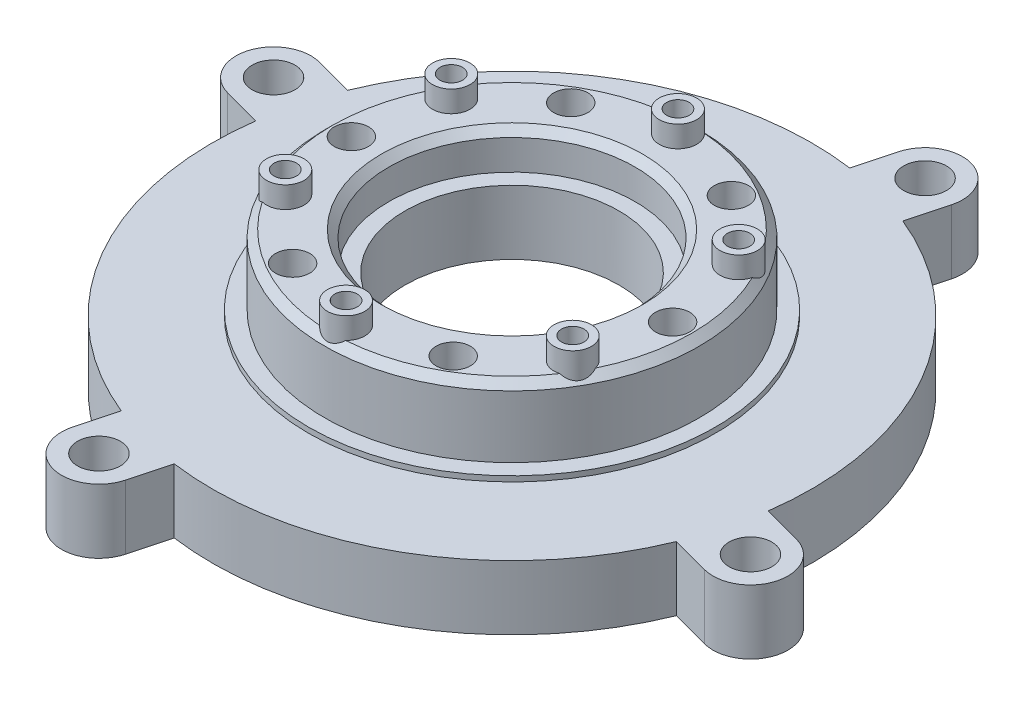
SolidWorks part; units mm, degrees
material "Like ABS"
ref_plane "Front Plane" through (0, 0, 0) normal (0, 0, 1) x (1, 0, 0)
ref_plane "Top Plane" through (0, 0, 0) normal (0, 1, 0) x (1, 0, 0)
ref_plane "Right Plane" through (0, 0, 0) normal (1, 0, 0) x (0, 0, -1)
sketch "Sketch1" plane through (0, 0, 0) normal (0, 1, 0) x (1, 0, 0)
  circle A0 centre (0, 0) radius 28
  dimension "D1" = 56
extrude "Boss-Extrude1" add sketch "Sketch1" along normal blind 6
sketch "Sketch2" plane through (0, 6, 0) normal (0, 1, 0) x (1, 0, 0)
  circle A0 centre (0, 0) radius 19
  dimension "D1" = 38
extrude "Boss-Extrude2" add sketch "Sketch2" along normal blind 0.5
sketch "Sketch3" plane through (0, 6.5, 0) normal (0, 1, 0) x (1, 0, 0)
  circle A0 centre (0, 0) radius 17.5
  dimension "D1" = 35
extrude "Boss-Extrude3" add sketch "Sketch3" along normal blind 6.5
sketch "Sketch4" plane through (0, 13, 0) normal (0, 1, 0) x (1, 0, 0)
  line L0 (0, 15.5) -> (0, 0) construction
  line L1 (0, 0) -> (7.75, 13.4234) construction
  circle A0 centre (0, 15.5) radius 1.05
  dimension "D3" = 2.1
  dimension "D1" = 30
  dimension "D2" = 15.5
extrude "Cut-Extrude1" cut sketch "Sketch4" against normal blind 3
pattern_circular "CirPattern1" count 6 over 360 about axis through (0, 13, 0) along (0, -1, 0) of "Cut-Extrude1"
sketch "Sketch5" plane through (0, 13, 0) normal (0, 1, 0) x (1, 0, 0)
  circle A0 centre (0, 0) radius 11.5
  dimension "D1" = 23
extrude "Cut-Extrude2" cut sketch "Sketch5" against normal blind 3.5
sketch "Sketch6" plane through (0, 9.5, 0) normal (0, 1, 0) x (1, 0, 0)
  circle A0 centre (0, 0) radius 10
  dimension "D1" = 20
extrude "Cut-Extrude3" cut sketch "Sketch6" against normal up to surface (9.5 mm away) up to face at (0, 0, 28)
sketch "Sketch7" plane through (0, 13, 0) normal (0, 1, 0) x (1, 0, 0)
  line L0 (0, 15.5) -> (0, 0) construction
  line L1 (0, 0) -> (7.5, 12.9904) construction
  circle A0 centre (7.5, 12.9904) radius 1.6
  dimension "D2" = 3.2
  dimension "D1" = 30
  dimension "D3" = 15
extrude "Cut-Extrude4" cut sketch "Sketch7" against normal up to surface (13 mm away) up to face at (0, 0, 10)
sketch "Sketch9" plane through (0, 0, 0) normal (0, -1, 0) x (1, 0, 0)
  line L1 (7.5, -9.6417) -> (4.6, -11.3161)
  line L2 (4.6, -11.3161) -> (4.6, -14.6647)
  line L3 (4.6, -14.6647) -> (7.5, -16.339)
  line L4 (7.5, -16.339) -> (10.4, -14.6647)
  line L5 (10.4, -14.6647) -> (10.4, -11.3161)
  line L6 (10.4, -11.3161) -> (7.5, -9.6417)
  circle A1 centre (7.5, -12.9904) radius 2.9 construction
  dimension "D1" = 5.8
extrude "Cut-Extrude10" cut sketch "Sketch9" against normal blind 5
chamfer "Chamfer1" distance 1 angle 45 1 edges at (0, 0, 10)
sketch "Sketch13" plane through (0, 6, 0) normal (0, 1, 0) x (1, 0, 0)
  line L0 (0, 25) -> (0, 0) construction
  line L1 (0, 0) -> (7.2469, 27.0459) construction
  line L2 (7.2469, 27.0459) -> (9.0587, 33.8074) construction
  line L6 (0, 0) -> (-27.0459, 7.2469) construction
  line L7 (-27.0459, 7.2469) -> (-33.8074, 9.0587) construction
  line L8 (0, 0) -> (-26.3114, 9.5766) construction
  line L9 (3.0505, 34.8668) -> (2.4404, 27.8935) construction
  line L10 (2.4404, 27.8935) -> (0, 0) construction
  line L11 (0, 0) -> (4.8621, 27.5746) construction
  line L12 (4.8621, 27.5746) -> (6.0777, 34.4683) construction
  line L19 (-26.3114, 9.5766) -> (-32.8892, 11.9707) construction
  line L20 (0, 0) -> (-25.3766, 11.8333) construction
  line L21 (-25.3766, 11.8333) -> (-31.7208, 14.7916) construction
  line L27 (4.7721, 31.3325) -> (3.0277, 24.8224)
  line L28 (3.0277, 24.8224) -> (9.7891, 23.0106)
  line L29 (9.7891, 23.0106) -> (11.5335, 29.5208)
  circle A0 centre (8.1528, 30.4267) radius 1.6
  circle A4 centre (0, 0) radius 28 construction
  arc A7 (11.5335, 29.5208) -> (4.7721, 31.3325) centre (8.1528, 30.4267) ccw
  dimension "D4" = 3.2
  dimension "D5" = 90
  dimension "D6" = 10
  dimension "D1" = 15
  dimension "D2" = 28
  dimension "D3" = 7
  dimension "D7" = 5
  dimension "D10" = 5
  dimension "D11" = 5
extrude "Boss-Extrude4" add sketch "Sketch13" against normal up to surface (6 mm away) up to face at (0, 0, 11)
sketch "Sketch14" plane through (0, 6, 0) normal (0, 1, 0) x (1, 0, 0)
  circle A0 centre (8.1528, 30.4267) radius 2
  dimension "D1" = 4
extrude "Cut-Extrude12" cut sketch "Sketch14" against normal blind 4
pattern_circular "CirPattern3" count 4 over 360 about axis through (0, 6, 0) along (0, -1, 0) of "Cut-Extrude12", "Boss-Extrude4"
sketch "Sketch15" plane through (0, 0, 0) normal (0, -1, 0) x (1, 0, 0)
  circle A0 centre (0, 0) radius 22.5
  dimension "D1" = 45
extrude "Cut-Extrude13" cut sketch "Sketch15" against normal blind 3.5
sketch "Sketch16" plane through (0, 13, 0) normal (0, 1, 0) x (1, 0, 0)
  circle A0 centre (0, 15.5) radius 1.05
  circle A1 centre (0, 15.5) radius 1.75
  dimension "D1" = 3.5
extrude "Boss-Extrude5" add sketch "Sketch16" along normal blind 2
pattern_circular "CirPattern4" count 6 over 360 about axis through (0, 9.5, 0) along (0, 1, 0) of "Boss-Extrude5" reverse direction yes
chamfer "Chamfer2" distance 0.7 angle 45 1 edges at (0, 13, 17.5)
chamfer "Chamfer3" distance 0.7 angle 45 1 edges at (0, 13, 11.5)
chamfer "Chamfer4" distance 1 angle 45 2 edges at (0, 0, -22.5) (0, 3.5, -22.5)
pattern_circular "CirPattern5" count 6 over 360 about axis through (0, -28.2843, 0) along (0, 1, 0) of "Cut-Extrude4", "Cut-Extrude10"
